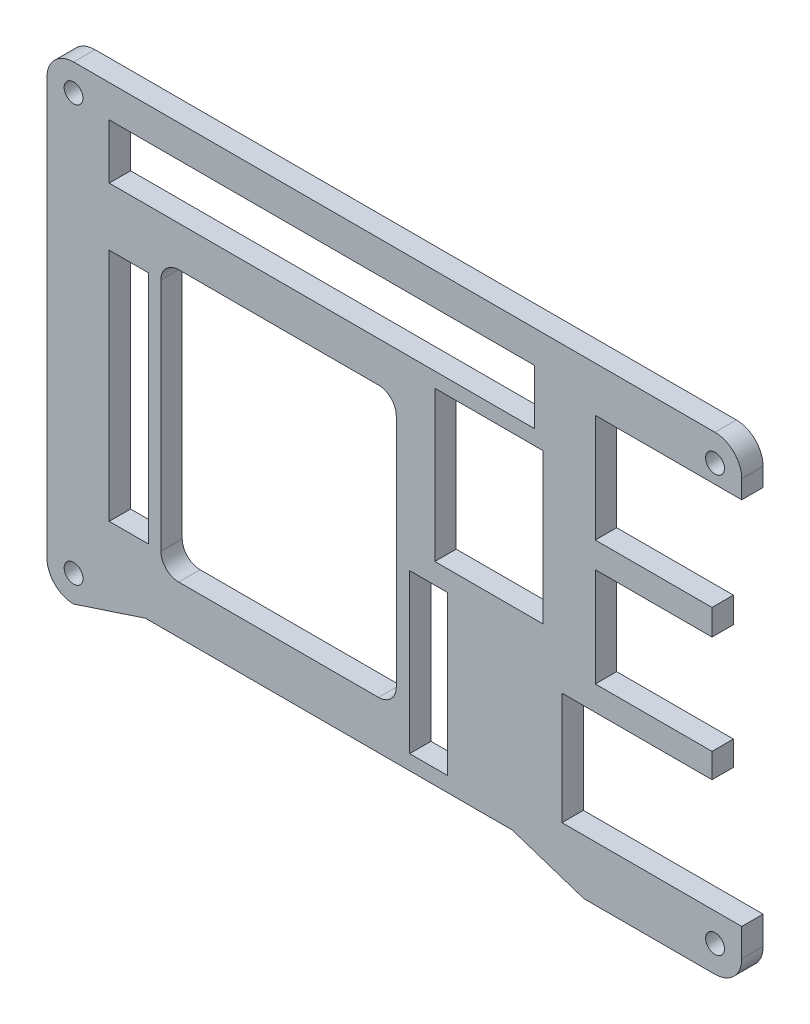
SolidWorks part; units mm, degrees
ref_plane "Front Plane" through (0, 0, 0) normal (0, 0, 1) x (1, 0, 0)
ref_plane "Top Plane" through (0, 0, 0) normal (0, 1, 0) x (1, 0, 0)
ref_plane "Right Plane" through (0, 0, 0) normal (1, 0, 0) x (0, 0, -1)
sketch "Sketch1" plane through (0, 0, 0) normal (0, 0, 1) x (1, 0, 0)
  line L0 (40.325, 24.0683) -> (61.2149, 24.0683) construction
  line L1 (40.325, 8.6582) -> (40.325, 24.0683) construction
  line L2 (56.975, 8.6582) -> (40.325, 8.6582) construction
  line L3 (56.975, 4.9979) -> (56.975, 8.6582) construction
  line L4 (40.325, 4.9979) -> (56.975, 4.9979) construction
  line L5 (40.325, -9.1218) -> (40.325, 4.9979) construction
  line L6 (56.975, -9.1218) -> (40.325, -9.1218) construction
  line L7 (56.975, -12.628) -> (56.975, -9.1218) construction
  line L8 (35.575, -12.628) -> (56.975, -12.628) construction
  line L9 (35.575, -28.6278) -> (35.575, -12.628) construction
  line L10 (61.2149, -28.6278) -> (35.575, -28.6278) construction
  line L11 (61.2149, -32.6134) -> (61.2149, -28.6278) construction
  line L12 (38.7143, -36.451) -> (57.405, -36.451) construction
  line L13 (28.4743, -33.0844) -> (38.7143, -36.451) construction
  line L14 (61.2149, 24.0683) -> (61.2149, 26.6839) construction
  line L15 (40.325, 24.0683) -> (61.2149, 24.0683)
  line L16 (40.325, 8.6582) -> (40.325, 24.0683)
  line L17 (56.975, 8.6582) -> (40.325, 8.6582)
  line L18 (56.975, 4.9979) -> (56.975, 8.6582)
  line L19 (40.325, 4.9979) -> (56.975, 4.9979)
  line L20 (40.325, -9.1218) -> (40.325, 4.9979)
  line L21 (56.975, -9.1218) -> (40.325, -9.1218)
  line L22 (56.975, -12.628) -> (56.975, -9.1218)
  line L23 (35.575, -12.628) -> (56.975, -12.628)
  line L24 (35.575, -28.6278) -> (35.575, -12.628)
  line L25 (61.2149, -28.6278) -> (35.575, -28.6278)
  line L26 (61.2149, -32.6134) -> (61.2149, -28.6278)
  line L27 (38.7143, -36.451) -> (57.405, -36.451)
  line L28 (28.4743, -33.0844) -> (38.7143, -36.451)
  line L29 (61.2149, 24.0683) -> (61.2149, 26.6839)
  line L30 (57.4049, 30.5077) -> (-34.0849, 30.5077) construction
  line L31 (-37.8949, 26.6977) -> (-37.8949, -32.641) construction
  line L32 (-34.0849, -36.451) -> (-23.8449, -33.0844) construction
  line L33 (57.4049, 30.5077) -> (-34.0849, 30.5077)
  line L34 (-37.8949, 26.6977) -> (-37.8949, -32.641)
  line L35 (-34.0849, -36.451) -> (-23.8449, -33.0844)
  line L36 (-23.8449, -33.0844) -> (28.4743, -33.0844)
  line L40 (13.845, -30.9668) -> (13.845, -8.3602)
  line L41 (13.845, -8.3602) -> (19.2484, -8.3602)
  line L42 (19.2484, -8.3602) -> (19.2484, -30.9668)
  line L43 (19.2484, -30.9668) -> (13.845, -30.9668)
  line L45 (-29.0049, 25.897) -> (31.6883, 25.897)
  line L46 (-29.0049, 25.897) -> (-29.0049, 18.087)
  line L47 (-29.0049, 18.087) -> (31.6883, 18.087)
  line L48 (31.6883, 25.897) -> (31.6883, 18.087)
  line L49 (17.441, 15.9724) -> (32.872, 15.9724)
  line L50 (17.441, 15.9724) -> (17.441, -5.4315)
  line L51 (17.441, -5.4315) -> (32.872, -5.4315)
  line L52 (32.872, 15.9724) -> (32.872, -5.4315)
  line L53 (-21.6389, 10.5941) -> (10.329, 10.5941)
  line L54 (-21.6389, 10.5941) -> (-21.6389, -7.643)
  line L55 (-21.6389, -7.643) -> (10.329, -7.643)
  line L56 (10.329, 10.5941) -> (10.329, -7.643)
  line L57 (-23.4169, 9.8012) -> (-29.0049, 9.8012)
  line L58 (-23.4169, 9.8012) -> (-23.4169, -23.6989)
  line L59 (-23.4169, -23.6989) -> (-29.0049, -23.6989)
  line L60 (-29.0049, 9.8012) -> (-29.0049, -23.6989)
  arc A0 (57.405, -36.451) -> (61.2149, -32.6134) centre (57.405, -32.641) ccw construction
  arc A1 (61.2149, 26.6839) -> (57.4049, 30.5077) centre (57.4049, 26.6977) ccw construction
  circle A2 centre (57.4049, 26.6977) radius 1.3462 construction
  circle A3 centre (57.405, -32.641) radius 1.3462 construction
  circle A4 centre (-34.0849, -32.641) radius 1.3462 construction
  circle A5 centre (-34.0849, 26.6977) radius 1.3462 construction
  arc A6 (57.405, -36.451) -> (61.2149, -32.6134) centre (57.405, -32.641) ccw
  arc A7 (61.2149, 26.6839) -> (57.4049, 30.5077) centre (57.4049, 26.6977) ccw
  circle A8 centre (57.4049, 26.6977) radius 1.3462
  circle A9 centre (57.405, -32.641) radius 1.3462
  circle A10 centre (-34.0849, -32.641) radius 1.3462
  circle A11 centre (-34.0849, 26.6977) radius 1.3462
  arc A12 (-34.0849, 30.5077) -> (-37.8949, 26.6977) centre (-34.0849, 26.6977) ccw construction
  arc A13 (-37.8949, -32.641) -> (-34.0849, -36.451) centre (-34.0849, -32.641) ccw construction
  arc A14 (-34.0849, 30.5077) -> (-37.8949, 26.6977) centre (-34.0849, 26.6977) ccw
  arc A15 (-37.8949, -32.641) -> (-34.0849, -36.451) centre (-34.0849, -32.641) ccw
extrude "Boss-Extrude1" add sketch "Sketch1" along normal blind 3.048
sketch "Sketch2" plane through (0, 0, 3.048) normal (0, 0, 1) x (1, 0, 0)
  line L0 (-21.6389, 10.5941) -> (-21.6389, -7.643) construction
  line L1 (11.94, 12.3412) -> (-21.6389, 12.3412)
  line L2 (11.94, 12.3412) -> (11.94, -26.2389)
  line L3 (11.94, -26.2389) -> (-21.6389, -26.2389)
  line L4 (-21.6389, 12.3412) -> (-21.6389, -26.2389)
  line L6 (-23.4169, 9.8012) -> (-29.0049, 9.8012) construction
  line L7 (-29.0049, -23.6989) -> (-23.4169, -23.6989) construction
  line L9 (-29.0049, -23.6989) -> (-23.4169, -23.6989) construction
  line L10 (13.845, -8.3602) -> (13.845, -30.9668) construction
  point P8 (-26.2109, -23.6989)
  dimension "D1" = 2.54
  dimension "D2" = 2.54
  dimension "D3" = 1.905
extrude "Cut-Extrude1" cut sketch "Sketch2" against normal through all
fillet "Fillet1" radius 2.54 4 edges at (11.94, -26.2389, 1.524) (-21.6389, -26.2389, 1.524) (-21.6389, 12.3412, 1.524) (11.94, 12.3412, 1.524)
